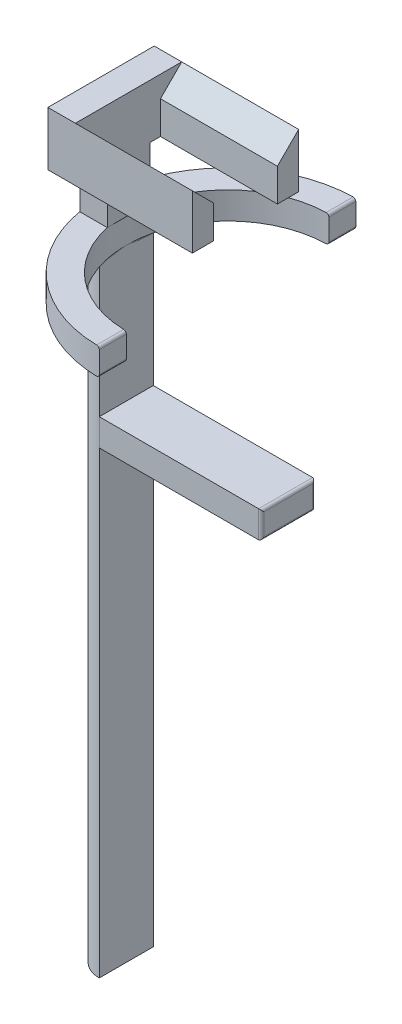
SolidWorks part; units mm, degrees
ref_plane "Front Plane" through (0, 0, 0) normal (0, 0, 1) x (1, 0, 0)
ref_plane "Top Plane" through (0, 0, 0) normal (0, 1, 0) x (1, 0, 0)
ref_plane "Right Plane" through (0, 0, 0) normal (1, 0, 0) x (0, 0, -1)
sketch "Sketch1" plane through (0, 0, 0) normal (0, 1, 0) x (0, 0, -1)
  line L0 (-120.65, 0) -> (120.65, 0)
  arc A0 (95.25, 0) -> (-95.25, 0) centre (0, 0) ccw
  arc A1 (120.65, 0) -> (-120.65, 0) centre (0, 0) ccw
  dimension "D1" = 190.5
  dimension "D2" = 241.3
extrude "Boss-Extrude1" add sketch "Sketch1" along normal blind 25.4 contours L0 A1 A0 region at (-117.9522, 0, 0)
sketch "Sketch4" plane through (0, 0, 0) normal (0, 0, 1) x (1, 0, 0)
  line L0 (-95.25, 0) -> (-120.65, 0)
  line L4 (-95.25, 0) -> (-95.25, -584.2)
  line L6 (-95.25, -584.2) -> (-120.65, -584.2)
  line L7 (-120.65, -584.2) -> (-120.65, 0)
  dimension "D2" = 584.2
revolve "Revolve1" add sketch "Sketch4" angle 180 mid plane about L4
sketch "Sketch5" plane through (-95.25, 0, 0) normal (1, 0, 0) x (0, 0, -1)
  line L0 (-95.25, 0) -> (0, 0) construction
  line L1 (-25.4, -127) -> (25.4, -127)
  line L2 (-25.4, -127) -> (-25.4, -152.4)
  line L3 (-25.4, -152.4) -> (25.4, -152.4)
  line L4 (25.4, -127) -> (25.4, -152.4)
  point P7 (0, -127)
  dimension "D1" = 127
  dimension "D2" = 50.8
  dimension "D3" = 25.4
extrude "Boss-Extrude3" add sketch "Sketch5" along normal blind 152.4
fillet "Fillet2" radius 2.54 4 edges at (57.15, -139.7, -25.4) (57.15, -152.4, 0) (57.15, -139.7, 25.4) (57.15, -127, 0)
fillet "Fillet6" radius 2.54 4 edges at (0, 0, -107.95) (0, 25.4, -107.95) (0, 0, 107.95) (0, 25.4, 107.95)
sketch "Sketch6" plane through (0, 25.4, 0) normal (0, 1, 0) x (1, 0, 0)
  line L0 (-120.65, 0) -> (54.61, 0) construction
  line L1 (54.61, -25.4) -> (54.61, 25.4) construction
  line L3 (-118.9808, 20) -> (-93.1266, 20)
  line L4 (-118.9808, 20) -> (-118.9808, -20)
  line L5 (-118.9808, -20) -> (-93.1266, -20)
  line L6 (-93.1266, 20) -> (-93.1266, -20)
  arc A0 (-2.54, 120.6233) -> (-2.54, -120.6233) centre (0, 0) ccw construction
  arc A1 (-2.54, 95.2161) -> (-2.54, -95.2161) centre (0, 0) ccw construction
  dimension "D1" = 20
  dimension "D2" = 20
extrude "Boss-Extrude4" add sketch "Sketch6" along normal blind 100
sketch "Sketch8" plane through (0, 0, -20) normal (0, 0, -1) x (-1, 0, 0)
  line L0 (118.9808, 125.4) -> (118.9808, 25.4) construction
  line L1 (93.1266, 125.4) -> (118.9808, 125.4)
  line L2 (93.1266, 125.4) -> (93.1266, 74.6)
  line L3 (93.1266, 74.6) -> (118.9808, 74.6)
  line L4 (118.9808, 125.4) -> (118.9808, 74.6)
  dimension "D1" = 50.8
extrude "Boss-Extrude5" add sketch "Sketch8" along normal blind 30.0101
sketch "Sketch9" plane through (0, 0, 20) normal (0, 0, 1) x (1, 0, 0)
  line L0 (-93.1266, 125.4) -> (-93.1266, 25.4) construction
  line L1 (-118.9808, 125.4) -> (-93.1266, 125.4)
  line L2 (-118.9808, 125.4) -> (-118.9808, 74.6)
  line L3 (-118.9808, 74.6) -> (-93.1266, 74.6)
  line L4 (-93.1266, 125.4) -> (-93.1266, 74.6)
  dimension "D1" = 50.8
extrude "Boss-Extrude6" add sketch "Sketch9" along normal blind 30.0101
sketch "Sketch11" plane through (-93.1266, 0, 0) normal (1, 0, 0) x (0, 0, -1)
  line L0 (30.0101, 105.4) -> (30.0101, 74.6)
  line L7 (50.0101, 125.4) -> (30.0101, 105.4)
  line L8 (50.0101, 74.6) -> (20, 74.6) construction
  line L9 (30.0101, 74.6) -> (50.0101, 74.6)
  line L10 (50.0101, 74.6) -> (50.0101, 125.4)
extrude "Boss-Extrude7" add sketch "Sketch11" along normal blind 110
sketch "Sketch12" plane through (-93.1266, 0, 0) normal (1, 0, 0) x (0, 0, -1)
  line L0 (-30.0101, 105.4) -> (-30.0101, 74.6)
  line L7 (-50.0101, 125.4) -> (-30.0101, 105.4)
  line L8 (-50.0101, 74.6) -> (-20, 74.6) construction
  line L9 (-30.0101, 74.6) -> (-50.0101, 74.6)
  line L10 (-50.0101, 74.6) -> (-50.0101, 125.4)
extrude "Boss-Extrude8" add sketch "Sketch12" along normal blind 110
fillet "Fillet7" radius 2.54 2 edges at (-95.25, 0, -12.7) (-95.25, 0, 12.7)
